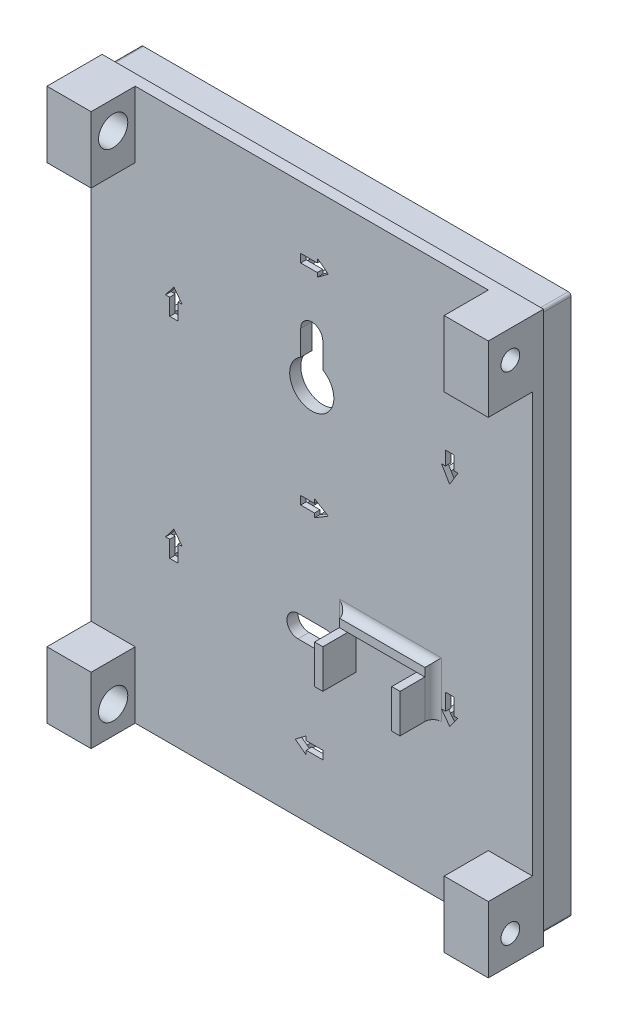
SolidWorks part; units mm, degrees
ref_plane "Front Plane" through (0, 0, 0) normal (0, 0, 1) x (1, 0, 0)
ref_plane "Top Plane" through (0, 0, 0) normal (0, 1, 0) x (1, 0, 0)
ref_plane "Right Plane" through (0, 0, 0) normal (1, 0, 0) x (0, 0, -1)
sketch "Sketch1" plane through (0, 0, 0) normal (0, 0, 1) x (1, 0, 0)
  line L0 (15.5, 38) -> (-15.5, 38) construction
  line L1 (40, 50) -> (-40, 50)
  line L2 (40, 50) -> (40, -50)
  line L3 (40, -50) -> (-40, -50)
  line L4 (-40, 50) -> (-40, -50)
  line L5 (0, 50) -> (0, -50) construction
  line L6 (15.5, 43.5) -> (15.5, 32.5)
  line L7 (15.5, -38) -> (-15.5, -38) construction
  line L260 (15.5, 43.5) -> (-15.5, 43.5)
  line L261 (15.5, 5.5) -> (-15.5, 5.5)
  line L262 (15.5, 5.5) -> (15.5, -5.5)
  line L263 (15.5, -5.5) -> (-15.5, -5.5)
  line L264 (-15.5, 5.5) -> (-15.5, -5.5)
  line L265 (0, -5.5) -> (0, 5.5) construction
  line L266 (15.5, 0) -> (-15.5, 0) construction
  line L271 (-15.5, 43.5) -> (-15.5, 32.5)
  line L272 (15.5, 32.5) -> (-15.5, 32.5)
  line L277 (15.5, -32.5) -> (15.5, -43.5)
  line L278 (15.5, -32.5) -> (-15.5, -32.5)
  line L283 (-15.5, -32.5) -> (-15.5, -43.5)
  line L284 (15.5, -43.5) -> (-15.5, -43.5)
  line L289 (25, 50) -> (25, -50) construction
  line L290 (7.7528, 32.5) -> (7.7528, 5.5) construction
  line L291 (30.5, 34.5) -> (19.5, 34.5)
  line L292 (30.5, 34.5) -> (30.5, 3.5)
  line L293 (30.5, 3.5) -> (19.5, 3.5)
  line L294 (19.5, 34.5) -> (19.5, 3.5)
  line L295 (25, 3.5) -> (25, 34.5) construction
  line L296 (30.5, 19) -> (19.5, 19) construction
  line L297 (-30.5, 3.5) -> (-19.5, 3.5)
  line L298 (-19.5, 34.5) -> (-19.5, 3.5)
  line L299 (-30.5, 34.5) -> (-19.5, 34.5)
  line L300 (-30.5, 34.5) -> (-30.5, 3.5)
  line L301 (-30.5, -34.5) -> (-30.5, -3.5)
  line L302 (-30.5, -34.5) -> (-19.5, -34.5)
  line L303 (-19.5, -34.5) -> (-19.5, -3.5)
  line L304 (-30.5, -3.5) -> (-19.5, -3.5)
  line L305 (30.5, -3.5) -> (19.5, -3.5)
  line L306 (19.5, -34.5) -> (19.5, -3.5)
  line L307 (30.5, -34.5) -> (19.5, -34.5)
  line L308 (30.5, -34.5) -> (30.5, -3.5)
  point P8 (0, 0)
  point P19 (25, 19)
  point P25 (7.7528, 19)
  dimension "D1" = 2
  dimension "D2" = 2
  dimension "D3" = 31
  dimension "D4" = 11
  dimension "D5" = 25
  dimension "D6" = 38
  dimension "D7" = 38
  dimension "D8" = 80
  dimension "D9" = 100
extrude "Boss-Extrude1" add sketch "Sketch1" along normal blind 1
sketch "Sketch2" plane through (0, 0, 1) normal (0, 0, 1) x (1, 0, 0)
  line L0 (40, 50) -> (-40, 50) construction
  line L1 (-40, 50) -> (-40, -50) construction
  line L2 (-40, -50) -> (40, -50) construction
  line L3 (40, -50) -> (40, 50) construction
  line L4 (40, 50) -> (-40, 50)
  line L5 (-40, 50) -> (-40, -50)
  line L6 (-40, -50) -> (40, -50)
  line L7 (40, -50) -> (40, 50)
extrude "back" add sketch "Sketch2" along normal blind 1
sketch "Sketch3" plane through (0, 0, 0) normal (0, 0, -1) x (-1, 0, 0)
  line L0 (-19.5, 3.5) -> (-19.5, 34.5) construction
  line L1 (-19.5, 34.5) -> (-30.5, 34.5) construction
  line L2 (-30.5, 34.5) -> (-30.5, 3.5) construction
  line L3 (-30.5, 3.5) -> (-19.5, 3.5) construction
  line L4 (15.5, -5.5) -> (15.5, 5.5) construction
  line L5 (15.5, 5.5) -> (-15.5, 5.5) construction
  line L6 (-15.5, 5.5) -> (-15.5, -5.5) construction
  line L7 (-15.5, -5.5) -> (15.5, -5.5) construction
  line L8 (-30.5, -3.5) -> (-30.5, -34.5) construction
  line L9 (-30.5, -34.5) -> (-19.5, -34.5) construction
  line L10 (-19.5, -34.5) -> (-19.5, -3.5) construction
  line L11 (-19.5, -3.5) -> (-30.5, -3.5) construction
  line L12 (-15.5, -43.5) -> (15.5, -43.5) construction
  line L13 (15.5, -43.5) -> (15.5, -32.5) construction
  line L14 (15.5, -32.5) -> (-15.5, -32.5) construction
  line L15 (-15.5, -32.5) -> (-15.5, -43.5) construction
  line L16 (19.5, -34.5) -> (30.5, -34.5) construction
  line L17 (30.5, -34.5) -> (30.5, -3.5) construction
  line L18 (30.5, -3.5) -> (19.5, -3.5) construction
  line L19 (19.5, -3.5) -> (19.5, -34.5) construction
  line L20 (30.5, 3.5) -> (30.5, 34.5) construction
  line L21 (30.5, 34.5) -> (19.5, 34.5) construction
  line L22 (19.5, 34.5) -> (19.5, 3.5) construction
  line L23 (19.5, 3.5) -> (30.5, 3.5) construction
  line L24 (-15.5, 32.5) -> (15.5, 32.5) construction
  line L25 (15.5, 32.5) -> (15.5, 43.5) construction
  line L26 (15.5, 43.5) -> (-15.5, 43.5) construction
  line L27 (-15.5, 43.5) -> (-15.5, 32.5) construction
  line L28 (15.5, -5.5) -> (15.5, 5.5)
  line L29 (15.5, 5.5) -> (-15.5, 5.5)
  line L30 (-15.5, 5.5) -> (-15.5, -5.5)
  line L31 (-15.5, -5.5) -> (15.5, -5.5)
  line L32 (-30.5, -3.5) -> (-30.5, -34.5)
  line L33 (-30.5, -34.5) -> (-19.5, -34.5)
  line L34 (-19.5, -34.5) -> (-19.5, -3.5)
  line L35 (-19.5, -3.5) -> (-30.5, -3.5)
  line L36 (-15.5, -43.5) -> (15.5, -43.5)
  line L37 (15.5, -43.5) -> (15.5, -32.5)
  line L38 (15.5, -32.5) -> (-15.5, -32.5)
  line L39 (-15.5, -32.5) -> (-15.5, -43.5)
  line L40 (19.5, -34.5) -> (30.5, -34.5)
  line L41 (30.5, -34.5) -> (30.5, -3.5)
  line L42 (30.5, -3.5) -> (19.5, -3.5)
  line L43 (19.5, -3.5) -> (19.5, -34.5)
  line L44 (30.5, 3.5) -> (30.5, 34.5)
  line L45 (30.5, 34.5) -> (19.5, 34.5)
  line L46 (19.5, 34.5) -> (19.5, 3.5)
  line L47 (19.5, 3.5) -> (30.5, 3.5)
  line L48 (-15.5, 32.5) -> (15.5, 32.5)
  line L49 (15.5, 32.5) -> (15.5, 43.5)
  line L50 (15.5, 43.5) -> (-15.5, 43.5)
  line L51 (-15.5, 43.5) -> (-15.5, 32.5)
  line L52 (-19.5, 3.5) -> (-19.5, 34.5)
  line L53 (-19.5, 34.5) -> (-30.5, 34.5)
  line L54 (-30.5, 34.5) -> (-30.5, 3.5)
  line L55 (-30.5, 3.5) -> (-19.5, 3.5)
  line L56 (-18.5, 2.5) -> (-18.5, 35.5)
  line L57 (-18.5, 35.5) -> (-31.5, 35.5)
  line L58 (-31.5, 35.5) -> (-31.5, 2.5)
  line L59 (-31.5, 2.5) -> (-18.5, 2.5)
  line L60 (-16.5, 31.5) -> (16.5, 31.5)
  line L61 (16.5, 31.5) -> (16.5, 44.5)
  line L62 (16.5, 44.5) -> (-16.5, 44.5)
  line L63 (-16.5, 44.5) -> (-16.5, 31.5)
  line L64 (31.5, 2.5) -> (31.5, 35.5)
  line L65 (31.5, 35.5) -> (18.5, 35.5)
  line L66 (18.5, 35.5) -> (18.5, 2.5)
  line L67 (18.5, 2.5) -> (31.5, 2.5)
  line L68 (16.5, -6.5) -> (16.5, 6.5)
  line L69 (16.5, 6.5) -> (-16.5, 6.5)
  line L70 (-16.5, 6.5) -> (-16.5, -6.5)
  line L71 (-16.5, -6.5) -> (16.5, -6.5)
  line L72 (-31.5, -2.5) -> (-31.5, -35.5)
  line L73 (-31.5, -35.5) -> (-18.5, -35.5)
  line L74 (-18.5, -35.5) -> (-18.5, -2.5)
  line L75 (-18.5, -2.5) -> (-31.5, -2.5)
  line L76 (-16.5, -44.5) -> (16.5, -44.5)
  line L77 (16.5, -44.5) -> (16.5, -31.5)
  line L78 (16.5, -31.5) -> (-16.5, -31.5)
  line L79 (-16.5, -31.5) -> (-16.5, -44.5)
  line L80 (18.5, -35.5) -> (31.5, -35.5)
  line L81 (31.5, -35.5) -> (31.5, -2.5)
  line L82 (31.5, -2.5) -> (18.5, -2.5)
  line L83 (18.5, -2.5) -> (18.5, -35.5)
  dimension "D1" = 1
  dimension "D2" = 1
  dimension "D3" = 1
  dimension "D4" = 1
  dimension "D5" = 1
  dimension "D6" = 1
  dimension "D7" = 1
extrude "seg masks" add sketch "Sketch3" along normal blind 6
sketch "Sketch5" plane through (0, 0, 0) normal (0, 0, -1) x (-1, 0, 0)
  line L0 (40, -50) -> (-40, -50) construction
  line L1 (40, 50) -> (40, -50) construction
  line L2 (-40, 50) -> (40, 50) construction
  line L3 (-40, -50) -> (-40, 50) construction
  line L4 (40, -50) -> (-40, -50) construction
  line L5 (40, 50) -> (40, -50) construction
  line L6 (-40, 50) -> (40, 50) construction
  line L7 (-40, -50) -> (-40, 50) construction
  line L8 (39, -49) -> (-39, -49)
  line L9 (-39, -49) -> (-39, 49)
  line L10 (-39, 49) -> (39, 49)
  line L11 (39, 49) -> (39, -49)
  line L12 (-38, 48) -> (38, 48)
  line L13 (38, 48) -> (38, -48)
  line L14 (38, -48) -> (-38, -48)
  line L15 (-38, -48) -> (-38, 48)
  dimension "D1" = 1
  dimension "D2" = 1
extrude "outer rim" add sketch "Sketch5" along normal blind 6
sketch "Sketch6" plane through (0, 0, 1) normal (0, 0, -1) x (-1, 0, 0)
  line L0 (-15.5, 38) -> (15.5, 38) construction
  line L1 (-15.5, 43.5) -> (-15.5, 32.5) construction
  line L2 (15.5, 43.5) -> (15.5, 32.5) construction
  line L3 (-1000, 0) -> (49000, 0) construction
  line L4 (25, 34.5) -> (25, -34.5) construction
  line L5 (30.5, 34.5) -> (19.5, 34.5) construction
  line L6 (19.5, -34.5) -> (30.5, -34.5) construction
  line L7 (-25, 35.5) -> (-25, -35.5) construction
  line L8 (-18.5, 35.5) -> (-31.5, 35.5) construction
  line L9 (-31.5, -35.5) -> (-18.5, -35.5) construction
  line L10 (-16.5, -38) -> (16.5, -38) construction
  line L11 (-16.5, -31.5) -> (-16.5, -44.5) construction
  line L12 (16.5, -44.5) -> (16.5, -31.5) construction
  line L20 (-31.5, 19) -> (31.5, 19) construction
  line L21 (-31.5, 35.5) -> (-31.5, 2.5) construction
  line L22 (31.5, 2.5) -> (31.5, 35.5) construction
  line L23 (-31.5, -19) -> (31.5, -19) construction
  line L24 (-31.5, -2.5) -> (-31.5, -35.5) construction
  line L25 (31.5, -35.5) -> (31.5, -2.5) construction
  line L26 (25, 22) -> (23.5, 20)
  line L27 (23.5, 20) -> (24.25, 20)
  line L28 (24.25, 20) -> (24.25, 17)
  line L29 (24.25, 17) -> (25.75, 17)
  line L30 (25.75, 20) -> (25.75, 17)
  line L31 (26.5, 20) -> (25.75, 20)
  line L32 (25, 22) -> (26.5, 20)
  line L33 (0, 44.5) -> (0, -44.5) construction
  line L34 (16.5, 44.5) -> (-16.5, 44.5) construction
  line L35 (-16.5, -44.5) -> (16.5, -44.5) construction
  line L36 (-3, 38) -> (-1, 36.5)
  line L37 (-1, 36.5) -> (-1, 37.25)
  line L38 (-1, 37.25) -> (2, 37.25)
  line L39 (2, 37.25) -> (2, 38.75)
  line L40 (-1, 38.75) -> (2, 38.75)
  line L41 (-1, 39.5) -> (-1, 38.75)
  line L42 (-3, 38) -> (-1, 39.5)
  line L43 (-24.25, 21) -> (-25.75, 21)
  line L44 (-25.75, 21) -> (-25.75, 18.5)
  line L45 (-25.75, 18.5) -> (-26.5, 18.5)
  line L46 (-26.5, 18.5) -> (-25, 16)
  line L47 (-24.25, 21) -> (-24.25, 18.5)
  line L48 (-24.25, 18.5) -> (-23.5, 18.5)
  line L49 (-23.5, 18.5) -> (-25, 16)
  line L50 (-24.25, -17) -> (-25.75, -17)
  line L51 (-25.75, -17) -> (-25.75, -20)
  line L52 (-25.75, -20) -> (-26.5, -20)
  line L53 (-26.5, -20) -> (-25, -22)
  line L54 (-23.5, -20) -> (-25, -22)
  line L55 (-24.25, -20) -> (-23.5, -20)
  line L56 (-24.25, -17) -> (-24.25, -20)
  line L57 (-2, -38.75) -> (-2, -37.25)
  line L58 (-2, -37.25) -> (1, -37.25)
  line L59 (1, -37.25) -> (1, -36.5)
  line L60 (1, -36.5) -> (3, -38)
  line L61 (1, -39.5) -> (3, -38)
  line L62 (1, -38.75) -> (1, -39.5)
  line L63 (-2, -38.75) -> (1, -38.75)
  line L64 (25, -16) -> (23.5, -18)
  line L65 (23.5, -18) -> (24.25, -18)
  line L66 (24.25, -18) -> (24.25, -21)
  line L67 (24.25, -21) -> (25.75, -21)
  line L68 (25.75, -18) -> (25.75, -21)
  line L69 (26.5, -18) -> (25.75, -18)
  line L70 (25, -16) -> (26.5, -18)
  line L71 (-0.5, 1.5) -> (-3, 0)
  line L72 (-0.5, 1.5) -> (-0.5, 0.75)
  line L73 (-0.5, 0.75) -> (2, 0.75)
  line L74 (2, 0.75) -> (2, 0)
  line L75 (2, -0.75) -> (2, 0)
  line L76 (-0.5, -0.75) -> (2, -0.75)
  line L77 (-0.5, -1.5) -> (-0.5, -0.75)
  line L78 (-0.5, -1.5) -> (-3, 0)
  point P45 (25, 17)
  point P59 (2, 38)
  point P67 (-25, 21)
  point P77 (-25, -17)
  point P85 (-2, -38)
  point P91 (25, -21)
  point P97 (2, 0.375)
  dimension "D1" = 5
  dimension "D2" = 2
  dimension "D3" = 1
  dimension "D4" = 1.5
  dimension "D5" = 0.75
  dimension "D6" = 5
  dimension "D7" = 2
  dimension "D8" = 1.5
  dimension "D9" = 1.5
  dimension "D10" = 1
  dimension "D11" = 5
  dimension "D12" = 2
  dimension "D13" = 1.5
  dimension "D14" = 1.5
  dimension "D15" = 1
  dimension "D16" = 5
  dimension "D17" = 2
  dimension "D18" = 1.5
  dimension "D19" = 3
  dimension "D20" = 1
  dimension "D21" = 5
  dimension "D22" = 2
  dimension "D23" = 1
  dimension "D24" = 1.5
  dimension "D25" = 1.5
  dimension "D26" = 5
  dimension "D27" = 1.5
  dimension "D28" = 1
  dimension "D29" = 3
  dimension "D30" = 2
  dimension "D31" = 1.5
  dimension "D32" = 5
  dimension "D33" = 2
  dimension "D34" = 1.5
  dimension "D35" = 3
  dimension "D36" = 1
extrude "direction" cut sketch "Sketch6" against normal through all both and the other way through all
sketch "Sketch7" plane through (0, 0, -6) normal (0, 0, -1) x (-1, 0, 0)
  line L0 (0, -1000) -> (0, -39.513) construction
  line L1 (-6.5, 46) -> (-3.5, 46)
  line L2 (-6.5, 46) -> (-6.5, 39.513)
  line L3 (-6.5, -46) -> (-3.5, -46)
  line L4 (-3.5, 46) -> (-3.5, 39.513)
  line L5 (16.5, 44.5) -> (-16.5, 44.5) construction
  line L6 (-16.5, -44.5) -> (16.5, -44.5) construction
  line L7 (6.5, -46) -> (3.5, -46)
  line L8 (3.5, 46) -> (3.5, 39.513)
  line L9 (6.5, 46) -> (3.5, 46)
  line L10 (6.5, 46) -> (6.5, 39.513)
  line L12 (-1025.0832, 19) -> (48974.9168, 19) construction
  line L13 (-33, 25.5) -> (-26.5, 25.5)
  line L14 (-33, 25.5) -> (-33, 22.5)
  line L15 (-33, 22.5) -> (-26.5, 22.5)
  line L16 (33, 25.5) -> (33, 22.5)
  line L17 (-31.5, 35.5) -> (-31.5, 2.5) construction
  line L18 (31.5, 2.5) -> (31.5, 35.5) construction
  line L19 (-33, 15.5) -> (-26.5, 15.5)
  line L20 (33, 12.5) -> (33, 15.5)
  line L21 (-33, 12.5) -> (-26.5, 12.5)
  line L22 (-33, 12.5) -> (-33, 15.5)
  line L23 (-33, -12.5) -> (-33, -15.5)
  line L24 (-33, -12.5) -> (-26.5, -12.5)
  line L25 (33, -12.5) -> (33, -15.5)
  line L26 (-33, -15.5) -> (-26.5, -15.5)
  line L27 (-33, -22.5) -> (-26.5, -22.5)
  line L28 (33, -25.5) -> (33, -22.5)
  line L29 (-33, -25.5) -> (-26.5, -25.5)
  line L30 (-33, -25.5) -> (-33, -22.5)
  line L31 (-6.5, 22.5) -> (-6.5, 15.5)
  line L32 (-3.5, 25.5) -> (3.5, 25.5)
  line L33 (-3.5, 22.5) -> (-3.5, 15.5)
  line L34 (-3.5, 22.5) -> (3.5, 22.5)
  line L35 (3.5, 22.5) -> (3.5, 15.5)
  line L36 (6.5, 22.5) -> (6.5, 15.5)
  line L37 (6.5, 25.5) -> (23.5, 25.5)
  line L38 (6.5, 22.5) -> (23.5, 22.5)
  line L39 (-6.5, 12.5) -> (-6.5, 1.5306)
  line L40 (-3.5, 12.5) -> (-3.5, 1.5306)
  line L41 (-3.5, 15.5) -> (3.5, 15.5)
  line L42 (-3.5, 12.5) -> (3.5, 12.5)
  line L43 (6.5, 15.5) -> (23.5, 15.5)
  line L44 (6.5, 12.5) -> (23.5, 12.5)
  line L45 (6.5, 12.5) -> (6.5, 1.5306)
  line L46 (3.5, 12.5) -> (3.5, 1.5306)
  line L47 (-6.5, -15.5) -> (-6.5, -22.5)
  line L48 (-3.5, -12.5) -> (3.5, -12.5)
  line L49 (-3.5, -15.5) -> (-3.5, -22.5)
  line L50 (-3.5, -15.5) -> (3.5, -15.5)
  line L51 (3.5, -15.5) -> (3.5, -22.5)
  line L52 (6.5, -12.5) -> (23.5, -12.5)
  line L53 (6.5, -15.5) -> (6.5, -22.5)
  line L54 (6.5, -15.5) -> (23.5, -15.5)
  line L55 (-3.5, -22.5) -> (3.5, -22.5)
  line L56 (-3.5, -25.5) -> (-3.5, -36.513)
  line L57 (-6.5, -25.5) -> (-6.5, -36.513)
  line L58 (-3.5, -25.5) -> (3.5, -25.5)
  line L59 (3.5, -25.5) -> (3.5, -36.513)
  line L60 (6.5, -22.5) -> (23.5, -22.5)
  line L61 (6.5, -25.5) -> (6.5, -36.513)
  line L62 (6.5, -25.5) -> (23.5, -25.5)
  line L63 (-18, -36.513) -> (-6.5, -36.513)
  line L64 (-18, 39.513) -> (-6.5, 39.513)
  line L65 (-18, 39.513) -> (-18, 36.513)
  line L66 (-18, 36.513) -> (-6.5, 36.513)
  line L67 (18, 39.513) -> (18, 36.513)
  line L68 (0, 36.513) -> (0, 39.513) construction
  line L69 (-18, 38.013) -> (18, 38.013) construction
  line L70 (-18, 1.5306) -> (-6.5, 1.5306)
  line L71 (-18, 1.5306) -> (-18, -1.4694)
  line L72 (-18, -1.4694) -> (-6.5, -1.4694)
  line L73 (18, 1.5306) -> (18, -1.4694)
  line L75 (-18, 0.0306) -> (18, 0.0306) construction
  line L76 (18, -39.513) -> (18, -36.513)
  line L77 (-18, -39.513) -> (-6.5, -39.513)
  line L78 (-18, -39.513) -> (-18, -36.513)
  line L79 (26.5, -37.5) -> (23.5, -37.5)
  line L80 (-26.5, 37.5) -> (-23.5, 37.5)
  line L81 (-26.5, 37.5) -> (-26.5, 25.5)
  line L82 (-26.5, -37.5) -> (-23.5, -37.5)
  line L83 (-23.5, 37.5) -> (-23.5, 25.5)
  line L84 (-25, -37.5) -> (-25, 37.5) construction
  line L86 (23.5, 37.5) -> (23.5, 25.5)
  line L87 (26.5, 37.5) -> (23.5, 37.5)
  line L88 (26.5, 37.5) -> (26.5, 25.5)
  line L89 (-3.5, 36.513) -> (3.5, 36.513)
  line L90 (-6.5, 36.513) -> (-6.5, 25.5)
  line L91 (-3.5, 36.513) -> (-3.5, 25.5)
  line L92 (-3.5, 39.513) -> (3.5, 39.513)
  line L93 (3.5, 36.513) -> (3.5, 25.5)
  line L94 (6.5, 36.513) -> (18, 36.513)
  line L95 (6.5, 36.513) -> (6.5, 25.5)
  line L96 (6.5, 39.513) -> (18, 39.513)
  line L97 (-23.5, 25.5) -> (-6.5, 25.5)
  line L98 (-23.5, 22.5) -> (-6.5, 22.5)
  line L99 (-26.5, 22.5) -> (-26.5, 15.5)
  line L100 (-23.5, 15.5) -> (-6.5, 15.5)
  line L101 (-23.5, 12.5) -> (-6.5, 12.5)
  line L102 (-26.5, 12.5) -> (-26.5, -12.5)
  line L103 (26.5, 25.5) -> (33, 25.5)
  line L104 (26.5, 22.5) -> (33, 22.5)
  line L105 (23.5, 22.5) -> (23.5, 15.5)
  line L106 (26.5, 22.5) -> (26.5, 15.5)
  line L107 (23.5, 12.5) -> (23.5, -12.5)
  line L108 (26.5, 12.5) -> (26.5, -12.5)
  line L109 (26.5, 15.5) -> (33, 15.5)
  line L110 (26.5, 12.5) -> (33, 12.5)
  line L111 (26.5, -12.5) -> (33, -12.5)
  line L112 (26.5, -15.5) -> (33, -15.5)
  line L113 (23.5, -15.5) -> (23.5, -22.5)
  line L114 (26.5, -15.5) -> (26.5, -22.5)
  line L115 (26.5, -22.5) -> (33, -22.5)
  line L116 (26.5, -25.5) -> (33, -25.5)
  line L117 (23.5, -25.5) -> (23.5, -37.5)
  line L118 (26.5, -25.5) -> (26.5, -37.5)
  line L119 (-26.5, -15.5) -> (-26.5, -22.5)
  line L120 (-23.5, -15.5) -> (-23.5, -22.5)
  line L121 (-23.5, -12.5) -> (-6.5, -12.5)
  line L122 (-23.5, -15.5) -> (-6.5, -15.5)
  line L123 (-23.5, -22.5) -> (-6.5, -22.5)
  line L124 (-23.5, -25.5) -> (-6.5, -25.5)
  line L125 (-26.5, -25.5) -> (-26.5, -37.5)
  line L126 (-23.5, -25.5) -> (-23.5, -37.5)
  line L127 (-3.5, -36.513) -> (3.5, -36.513)
  line L128 (-3.5, -39.513) -> (3.5, -39.513)
  line L129 (6.5, -36.513) -> (18, -36.513)
  line L130 (6.5, -39.513) -> (18, -39.513)
  line L131 (-6.5, -39.513) -> (-6.5, -46)
  line L132 (-3.5, -39.513) -> (-3.5, -46)
  line L134 (3.5, -39.513) -> (3.5, -46)
  line L135 (-23.5, 22.5) -> (-23.5, 15.5)
  line L136 (-23.5, 12.5) -> (-23.5, -12.5)
  line L137 (6.5, -39.513) -> (6.5, -46)
  line L140 (-3.5, 1.5306) -> (3.5, 1.5306)
  line L141 (-6.5, -1.4694) -> (-6.5, -12.5)
  line L142 (-3.5, -1.4694) -> (-3.5, -12.5)
  line L143 (-3.5, -1.4694) -> (3.5, -1.4694)
  line L144 (3.5, -1.4694) -> (3.5, -12.5)
  line L145 (6.5, -1.4694) -> (6.5, -12.5)
  line L148 (6.5, 1.5306) -> (18, 1.5306)
  line L149 (6.5, -1.4694) -> (18, -1.4694)
  point P5 (-5, 46)
  point P73 (0, 38.013)
  point P77 (0, 0.0306)
  dimension "D1" = 3
  dimension "D2" = 3.5
  dimension "D3" = 1.5
  dimension "D4" = 1.5
  dimension "D5" = 3
  dimension "D7" = 1.5
  dimension "D8" = 1.5
  dimension "D9" = 3
  dimension "D10" = 36
  dimension "D11" = 3
  dimension "D12" = 75
  dimension "D13" = 25
extrude "wire chases" cut sketch "Sketch7" against normal up to surface (6 mm away) up to face at (0, 0, 0)
sketch "Sketch8" plane through (0, 0, 0) normal (0, 0, -1) x (-1, 0, 0)
  line L0 (0, -1000) -> (0, 49000) construction
  line L3 (0, 27) -> (0, 22) construction
  line L4 (2, 27) -> (2, 22.4641)
  line L5 (-2, 27) -> (-2, 22.4641)
  arc A2 (2, 27) -> (-2, 27) centre (0, 27) ccw
  arc A4 (-2, 22.4641) -> (2, 22.4641) centre (0, 19) ccw
  point P4 (0, 22)
  dimension "D1" = 2
  dimension "D2" = 5
  dimension "D4" = 8
  dimension "D3" = 22
extrude "hanging hole" cut sketch "Sketch8" against normal through all both and the other way through all
fillet "Fillet1" radius 0.5 8 edges at (38, -48, -3) (38, 48, -3) (-38, 48, -3) (-38, -48, -3) (-39, -49, -3) (39, -49, -3) (-39, 49, -3) (39, 49, -3)
sketch "Sketch9" plane through (0, 0, 2) normal (0, 0, 1) x (1, 0, 0)
  line L1 (-40, 50) -> (-32, 50)
  line L2 (-40, 50) -> (-40, 38)
  line L3 (-40, 38) -> (-32, 38)
  line L4 (-32, 50) -> (-32, 38)
  line L5 (-40, -50) -> (-32, -50)
  line L6 (-40, -50) -> (-40, -38)
  line L7 (-40, -38) -> (-32, -38)
  line L8 (-32, -50) -> (-32, -38)
  line L9 (40, -50) -> (32, -50)
  line L10 (40, -50) -> (40, -38)
  line L11 (40, -38) -> (32, -38)
  line L12 (32, -50) -> (32, -38)
  line L13 (40, 50) -> (32, 50)
  line L14 (40, 50) -> (40, 38)
  line L15 (40, 38) -> (32, 38)
  line L16 (32, 50) -> (32, 38)
  dimension "D1" = 8
  dimension "D2" = 12
extrude "Boss-Extrude2" add sketch "Sketch9" along normal blind 8
sketch "Sketch10" plane through (40, 0, 0) normal (1, 0, 0) x (0, 0, -1)
  line L0 (-10, 38) -> (-10, 50) construction
  line L1 (-10, 50) -> (0, 50) construction
  line L5 (-1000, 0) -> (49000, 0) construction
  circle A0 centre (-6, 45) radius 1.7
  circle A1 centre (-6, -45) radius 1.7
  dimension "D1" = 3.4
  dimension "D2" = 4
  dimension "D3" = 5
extrude "Cut-Extrude1" cut sketch "Sketch10" against normal through all both and the other way through all
sketch "Sketch11" plane through (-32, 0, 0) normal (1, 0, 0) x (0, 0, -1)
  circle A0 centre (-6, 45) radius 2.65
  dimension "D1" = 5.3
extrude "Cut-Extrude2" cut sketch "Sketch11" against normal blind 3.9
mirror "Mirror1" about plane through (0, 0, 0) normal (0, 1, 0) of "Cut-Extrude2"
mirror "Mirror2" about plane through (0, 0, 0) normal (1, 0, 0) of "Cut-Extrude2"
mirror "Mirror4" about plane through (0, 0, 0) normal (1, 0, 0) of "Mirror1"
sketch "Sketch12" plane through (0, 0, 2) normal (0, 0, 1) x (1, 0, 0)
  line L1 (6.5, -15) -> (8, -15)
  line L2 (6.5, -15) -> (6.5, -22)
  line L3 (6.5, -22) -> (8, -22)
  line L4 (8, -15) -> (8, -22)
  line L5 (20.5, -15) -> (22, -15)
  line L6 (20.5, -15) -> (20.5, -22)
  line L7 (20.5, -22) -> (22, -22)
  line L8 (22, -15) -> (22, -22)
  dimension "D1" = 12.5
  dimension "D2" = 7
  dimension "D3" = 1.5
  dimension "D4" = 15
  dimension "D5" = 6.5
extrude "Boss-Extrude3" add sketch "Sketch12" along normal blind 6
sketch "Sketch13" plane through (0, 0, 2) normal (0, 0, 1) x (1, 0, 0)
  line L0 (22, -22) -> (22, -15) construction
  line L1 (6.5, -15) -> (22, -15)
  line L2 (6.5, -15) -> (6.5, -13.5)
  line L3 (6.5, -13.5) -> (22, -13.5)
  line L4 (22, -15) -> (22, -13.5)
  line L5 (6.5, -22) -> (8, -22) construction
extrude "Boss-Extrude4" add sketch "Sketch13" along normal blind 1.5
fillet "Fillet2" radius 1.5 3 edges at (22, -17.75, 2) (14.25, -13.5, 2) (6.5, -17.75, 2)
sketch "Sketch14" plane through (0, 0, 0) normal (0, 0, -1) x (-1, 0, 0)
  line L0 (-2.5, -20) -> (2.5, -20) construction
  line L1 (-2.5, -18) -> (2.5, -18)
  line L2 (-2.5, -22) -> (2.5, -22)
  line L3 (0, -1000) -> (0, 49000) construction
  arc A0 (-2.5, -18) -> (-2.5, -22) centre (-2.5, -20) ccw
  arc A1 (2.5, -22) -> (2.5, -18) centre (2.5, -20) ccw
  point P2 (0, -20)
  dimension "D2" = 2
  dimension "D1" = 20
  dimension "D3" = 5
extrude "Cut-Extrude3" cut sketch "Sketch14" against normal through all both and the other way through all
